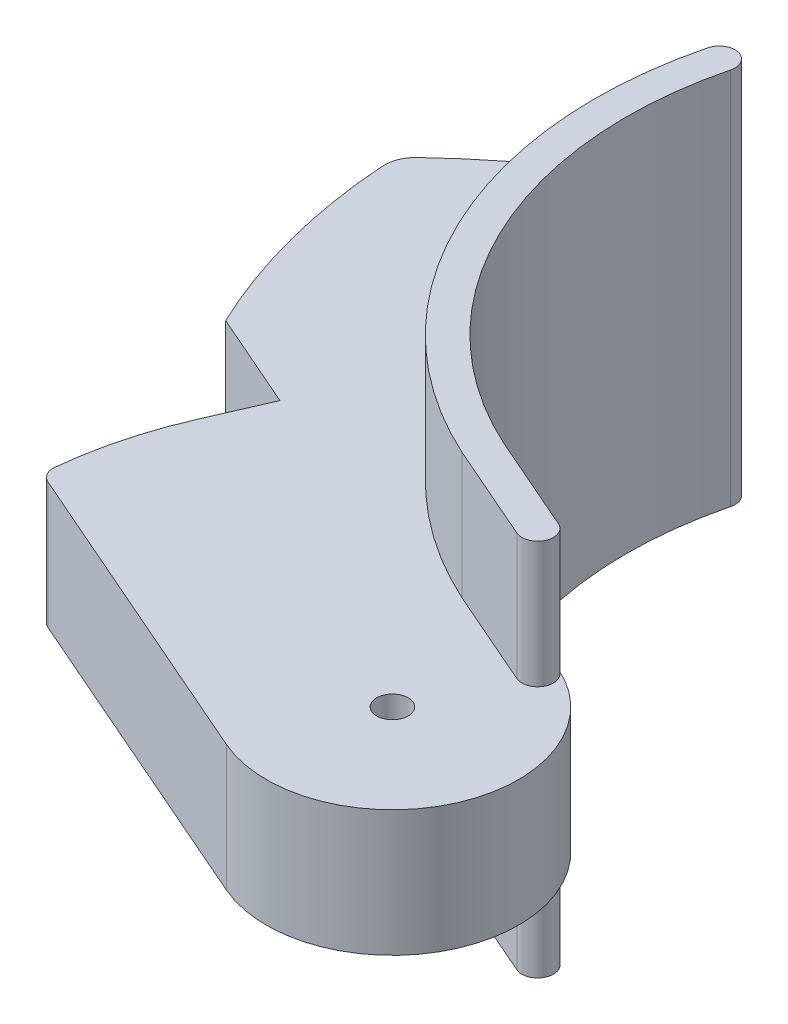
SolidWorks part; units mm, degrees
ref_plane "Plan de face" through (0, 0, 0) normal (0, 0, 1) x (1, 0, 0)
ref_plane "Plan de dessus" through (0, 0, 0) normal (0, 1, 0) x (1, 0, 0)
ref_plane "Plan de droite" through (0, 0, 0) normal (1, 0, 0) x (0, 0, -1)
sketch "Esquisse1" plane through (0, 0, 0) normal (0, 1, 0) x (1, 0, 0)
  line L0 (-21.1447, 0) -> (21.1447, 0) construction
  line L2 (0, 107.7631) -> (107.7631, 0) construction
  line L9 (0, 76.2) -> (0, -76.2) construction
  line L10 (22.4506, 85.3124) -> (49.3914, 112.2532) construction
  line L11 (112.2532, 49.3914) -> (49.3914, 112.2532) construction
  line L12 (85.3124, 22.4506) -> (22.4506, 85.3124) construction
  line L13 (85.3124, 22.4506) -> (112.2532, 49.3914) construction
  line L14 (0, 107.7631) -> (107.7631, 0) construction
  line L15 (0, -76.2) -> (0, -166.9225) construction
  line L16 (12.0681, -77.8609) -> (31.5678, -69.3535) construction
  line L17 (32.3819, -124.4225) -> (154.4572, -71.1636) construction
  line L18 (22.225, -101.1417) -> (-24.6748, 6.3579) construction
  line L19 (37.6806, 33.5622) -> (-24.6748, 6.3579) construction
  line L22 (31.5678, -69.3535) -> (134.1433, -24.602) construction
  line L26 (-73.8821, 18.6512) -> (13.4209, -19.4373) construction
  line L27 (-86.989, -59.0305) -> (-106.4228, -50.5519)
  line L28 (-37.6806, 33.5622) -> (24.6748, 6.3579) construction
  line L29 (-22.225, -101.1417) -> (24.6748, 6.3579) construction
  line L30 (-32.3819, -124.4225) -> (-96.1391, -96.6066)
  line L32 (73.8821, 18.6512) -> (-13.4209, -19.4373) construction
  line L33 (92.0675, -70.6709) -> (86.989, -59.0305) construction
  line L34 (86.989, -59.0305) -> (106.4228, -50.5519) construction
  line L35 (0, 107.7631) -> (-107.7631, 0) construction
  line L36 (-85.3124, 22.4506) -> (-112.2532, 49.3914) construction
  line L37 (-85.3124, 22.4506) -> (-22.4506, 85.3124) construction
  line L38 (-112.2532, 49.3914) -> (-49.3914, 112.2532) construction
  line L39 (-22.4506, 85.3124) -> (-49.3914, 112.2532) construction
  line L40 (0, 107.7631) -> (-107.7631, 0) construction
  line L41 (-92.0675, -70.6709) -> (-86.989, -59.0305)
  line L42 (-12.0681, -77.8609) -> (-31.5678, -69.3535)
  line L43 (22.225, -101.1417) -> (-22.225, -101.1417) construction
  circle A2 centre (22.225, -101.1417) radius 22.225 construction
  arc A3 (154.4572, -71.1636) -> (37.6806, 33.5622) centre (22.225, -101.1417) ccw construction
  circle A4 centre (22.225, -101.1417) radius 25.4 construction
  arc A5 (77.9162, -49.1327) -> (98.23, -95.6944) centre (22.225, -101.1417) cw construction
  arc A6 (112.8374, -33.8973) -> (117.7176, -4.8858) centre (0, 0) ccw construction
  arc A7 (115.5939, -2.8245) -> (117.557, -7.8522) centre (111.2211, -7.429) cw construction
  arc A8 (73.8821, 18.6512) -> (78.273, 22.3194) centre (76.9606, 19.4284) cw construction
  arc A14 (0, -76.2) -> (0, 76.2) centre (0, 0) ccw construction
  arc A17 (112.8374, -33.8973) -> (106.4228, -50.5519) centre (0, 0) cw construction
  arc A18 (-73.8821, 18.6512) -> (-78.273, 22.3194) centre (-76.9606, 19.4284) ccw
  arc A19 (-115.5939, -2.8245) -> (-117.557, -7.8522) centre (-111.2211, -7.429) ccw
  arc A20 (-112.8374, -33.8973) -> (-117.557, -7.8522) centre (0, 0) cw
  arc A21 (-92.0675, -70.6709) -> (-98.0279, -93.3728) centre (-22.225, -101.1417) ccw
  arc A22 (-12.0681, -77.8609) -> (-32.3819, -124.4225) centre (-22.225, -101.1417) cw
  arc A23 (-73.8821, 18.6512) -> (-31.5678, -69.3535) centre (0, 0) ccw
  circle A24 centre (-22.225, -101.1417) radius 22.225 construction
  arc A25 (-115.5939, -2.8245) -> (-78.273, 22.3194) centre (-22.225, -101.1417) cw
  arc A26 (-112.8374, -33.8973) -> (-106.4228, -50.5519) centre (0, 0) ccw
  circle A27 centre (94.8695, -93.6965) radius 3.175 construction
  arc A28 (-96.1391, -96.6066) -> (-98.0279, -93.3728) centre (-94.8695, -93.6965) cw
  dimension "D5" = 3.175
  dimension "D6" = 44.45
  dimension "D8" = 50.8
  dimension "D9" = 76.2
  dimension "D11" = 3.175
  dimension "D12" = 6.35
  dimension "D10" = 38.1
  dimension "D14" = 76.2
  dimension "D17" = 6.35
  dimension "D2" = 38.1
  dimension "D3" = 88.9
  dimension "D4" = 38.1
  dimension "D7" = 95.25
  dimension "D13" = 152.4
  dimension "D15" = 31.75
  dimension "D16" = 12.7
extrude "Boss.-Extru.1" add sketch "Esquisse1" along normal blind 25.4
sketch "Esquisse2" plane through (0, 25.4, 0) normal (0, 1, 0) x (1, 0, 0)
  line L3 (-12.0681, -77.8609) -> (-31.5678, -69.3535) construction
  line L6 (-12.0681, -77.8609) -> (-31.5678, -69.3535)
  line L7 (-14.6073, -83.6811) -> (-34.152, -75.1541)
  arc A3 (-73.8821, 18.6512) -> (-31.5678, -69.3535) centre (0, 0) ccw construction
  arc A9 (-73.8821, 18.6512) -> (-31.5678, -69.3535) centre (0, 0) ccw
  arc A10 (-80.039, 20.2055) -> (-34.152, -75.1541) centre (0, 0) ccw
  arc A11 (-73.8821, 18.6512) -> (-80.039, 20.2055) centre (-76.9606, 19.4284) ccw
  arc A12 (-12.0681, -77.8609) -> (-14.6073, -83.6811) centre (-13.3377, -80.771) cw
  dimension "D1" = 6.35
extrude "Boss.-Extru.3" add sketch "Esquisse2" along normal blind 25.4 and the other way blind 50.8
sketch "Esquisse4" plane through (0, 25.4, 0) normal (0, 1, 0) x (1, 0, 0)
  circle A0 centre (-22.225, -101.1417) radius 3.175
  arc A1 (-32.3819, -124.4225) -> (-12.0681, -77.8609) centre (-22.225, -101.1417) ccw construction
  dimension "D1" = 6.35
extrude "Enlèv. mat.-Extru.2" cut sketch "Esquisse4" against normal through all
